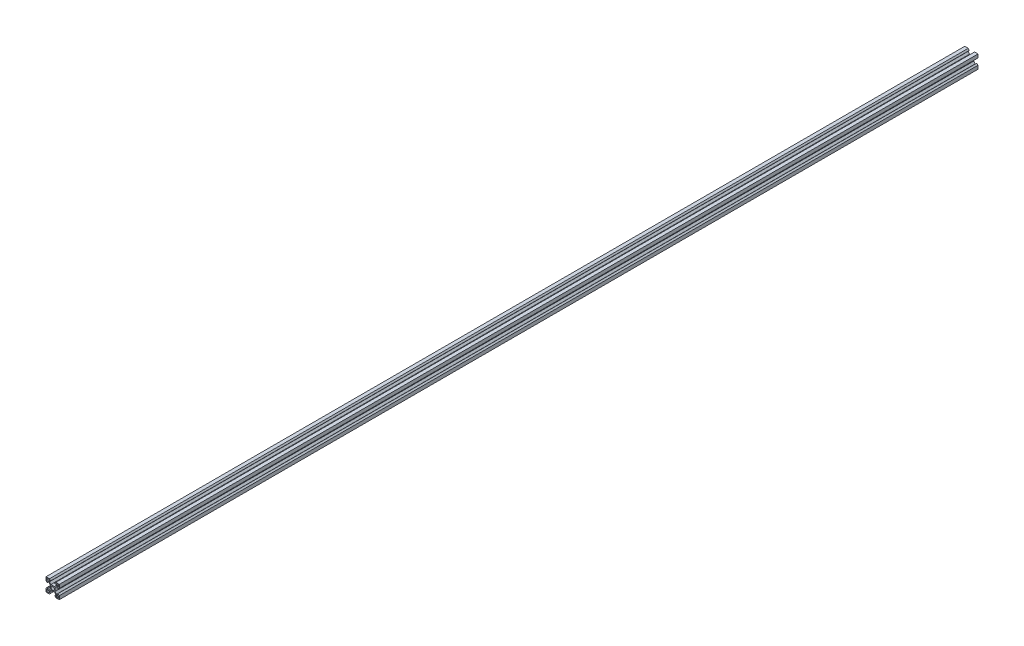
SolidWorks part; units mm, degrees
ref_plane "Спереди" through (0, 0, 0) normal (0, 0, 1) x (1, 0, 0)
ref_plane "Сверху" through (0, 0, 0) normal (0, 1, 0) x (1, 0, 0)
ref_plane "Справа" through (0, 0, 0) normal (1, 0, 0) x (0, 0, -1)
sketch "Эскиз1" plane through (0, 0, 0) normal (0, 0, 1) x (1, 0, 0)
  line L0 (-7.5, 7.5) -> (7.5, 7.5) construction
  line L1 (-10, -10) -> (10, -10) construction
  line L2 (-10, -10) -> (-10, 10) construction
  line L3 (-10, 10) -> (-4.75, 10)
  line L4 (10, -10) -> (10, 10) construction
  line L5 (-10, -10) -> (10, 10) construction
  line L6 (-10, 10) -> (10, -10) construction
  line L7 (7.5, 7.5) -> (7.5, -7.5) construction
  line L8 (7.5, -7.5) -> (-7.5, -7.5) construction
  line L9 (-7.5, -7.5) -> (-7.5, 7.5) construction
  line L10 (-7.5, 7.5) -> (7.5, -7.5) construction
  line L11 (-7.5, -7.5) -> (7.5, 7.5) construction
  line L12 (-4.75, 10) -> (-3.1, 8)
  line L13 (-3.1, 8) -> (-4.95, 8)
  line L14 (-4.95, 8) -> (-4.95, 5.85)
  line L15 (-4.95, 5.85) -> (-2.6, 3.5)
  line L16 (-2.6, 3.5) -> (2.6, 3.5)
  line L17 (2.6, 3.5) -> (4.95, 5.85)
  line L18 (4.95, 5.85) -> (4.95, 8)
  line L19 (4.95, 8) -> (3.1, 8)
  line L20 (3.1, 8) -> (4.75, 10)
  line L21 (4.75, 10) -> (10, 10)
  line L22 (-4.75, 10) -> (4.75, 10) construction
  line L23 (-3.1, 8) -> (3.1, 8) construction
  line L24 (-4.95, 5.85) -> (4.95, 5.85) construction
  line L25 (-2.6, 3.5) -> (0, 0) construction
  line L26 (-9.15, 5.85) -> (-5.85, 5.85)
  line L27 (-9.15, 5.85) -> (-9.15, 9.15)
  line L28 (-9.15, 9.15) -> (-5.85, 9.15)
  line L29 (-5.85, 5.85) -> (-5.85, 9.15)
  line L30 (-9.15, 5.85) -> (-5.85, 9.15) construction
  line L31 (-9.15, 9.15) -> (-5.85, 5.85) construction
  line L32 (9.15, 5.85) -> (5.85, 5.85)
  line L33 (9.15, 5.85) -> (9.15, 9.15)
  line L34 (9.15, 9.15) -> (5.85, 9.15)
  line L35 (5.85, 5.85) -> (5.85, 9.15)
  line L36 (9.15, 5.85) -> (5.85, 9.15) construction
  line L37 (9.15, 9.15) -> (5.85, 5.85) construction
  line L38 (9.15, -9.15) -> (5.85, -9.15)
  line L39 (9.15, -9.15) -> (9.15, -5.85)
  line L40 (9.15, -5.85) -> (5.85, -5.85)
  line L41 (5.85, -9.15) -> (5.85, -5.85)
  line L42 (9.15, -9.15) -> (5.85, -5.85) construction
  line L43 (9.15, -5.85) -> (5.85, -9.15) construction
  line L44 (-9.15, -5.85) -> (-5.85, -5.85)
  line L45 (-9.15, -5.85) -> (-9.15, -9.15)
  line L46 (-9.15, -9.15) -> (-5.85, -9.15)
  line L47 (-5.85, -5.85) -> (-5.85, -9.15)
  line L48 (-9.15, -5.85) -> (-5.85, -9.15) construction
  line L49 (-9.15, -9.15) -> (-5.85, -5.85) construction
  line L50 (3.5, 2.6) -> (0, 0) construction
  line L51 (3.5, 2.6) -> (3.5, -2.6)
  line L52 (5.85, 4.95) -> (3.5, 2.6)
  line L53 (3.5, -2.6) -> (5.85, -4.95)
  line L54 (5.85, -4.95) -> (8, -4.95)
  line L55 (8, -4.95) -> (8, -3.1)
  line L56 (8, -3.1) -> (10, -4.75)
  line L57 (8, 4.95) -> (5.85, 4.95)
  line L58 (8, 3.1) -> (8, 4.95)
  line L59 (10, 4.75) -> (8, 3.1)
  line L60 (2.6, -3.5) -> (0, 0) construction
  line L61 (2.6, -3.5) -> (-2.6, -3.5)
  line L62 (4.95, -5.85) -> (2.6, -3.5)
  line L63 (-2.6, -3.5) -> (-4.95, -5.85)
  line L64 (-4.95, -5.85) -> (-4.95, -8)
  line L65 (-4.95, -8) -> (-3.1, -8)
  line L66 (-3.1, -8) -> (-4.75, -10)
  line L67 (4.95, -8) -> (4.95, -5.85)
  line L68 (3.1, -8) -> (4.95, -8)
  line L69 (4.75, -10) -> (3.1, -8)
  line L70 (-3.5, -2.6) -> (0, 0) construction
  line L71 (-3.5, -2.6) -> (-3.5, 2.6)
  line L72 (-5.85, -4.95) -> (-3.5, -2.6)
  line L73 (-3.5, 2.6) -> (-5.85, 4.95)
  line L74 (-5.85, 4.95) -> (-8, 4.95)
  line L75 (-8, 4.95) -> (-8, 3.1)
  line L76 (-8, 3.1) -> (-10, 4.75)
  line L77 (-8, -4.95) -> (-5.85, -4.95)
  line L78 (-8, -3.1) -> (-8, -4.95)
  line L79 (-10, -4.75) -> (-8, -3.1)
  line L80 (-10, 10) -> (-10, 4.75)
  line L81 (-10, -4.75) -> (-10, -10)
  line L82 (-10, -10) -> (-4.75, -10)
  line L83 (4.75, -10) -> (10, -10)
  line L84 (10, -10) -> (10, -4.75)
  line L85 (10, 4.75) -> (10, 10)
  circle A0 centre (-7.5, 7.5) radius 1.65 construction
  circle A1 centre (7.5, 7.5) radius 1.65 construction
  circle A2 centre (7.5, -7.5) radius 1.65 construction
  circle A3 centre (-7.5, -7.5) radius 1.65 construction
  circle A4 centre (0, 0) radius 2.5
  point P0 (0, 0)
  point P14 (0, 0)
  point P15 (0, 3.5)
  point P26 (0, 5.85)
  point P27 (0, 8)
  point P28 (0, 10)
  point P80 (0, 0)
  dimension "D3" = 3.3
  dimension "D4" = 3.3
  dimension "D5" = 3.3
  dimension "D6" = 3.3
  dimension "D14" = 5
  dimension "D1" = 20
  dimension "D2" = 20
  dimension "D7" = 15
  dimension "D8" = 6.2
  dimension "D9" = 9.9
  dimension "D10" = 9.5
  dimension "D11" = 2
  dimension "D12" = 6.5
  dimension "D15" = 4
extrude "Бобышка-Вытянуть1" add sketch "Эскиз1" against normal up to surface (1384 mm away)
